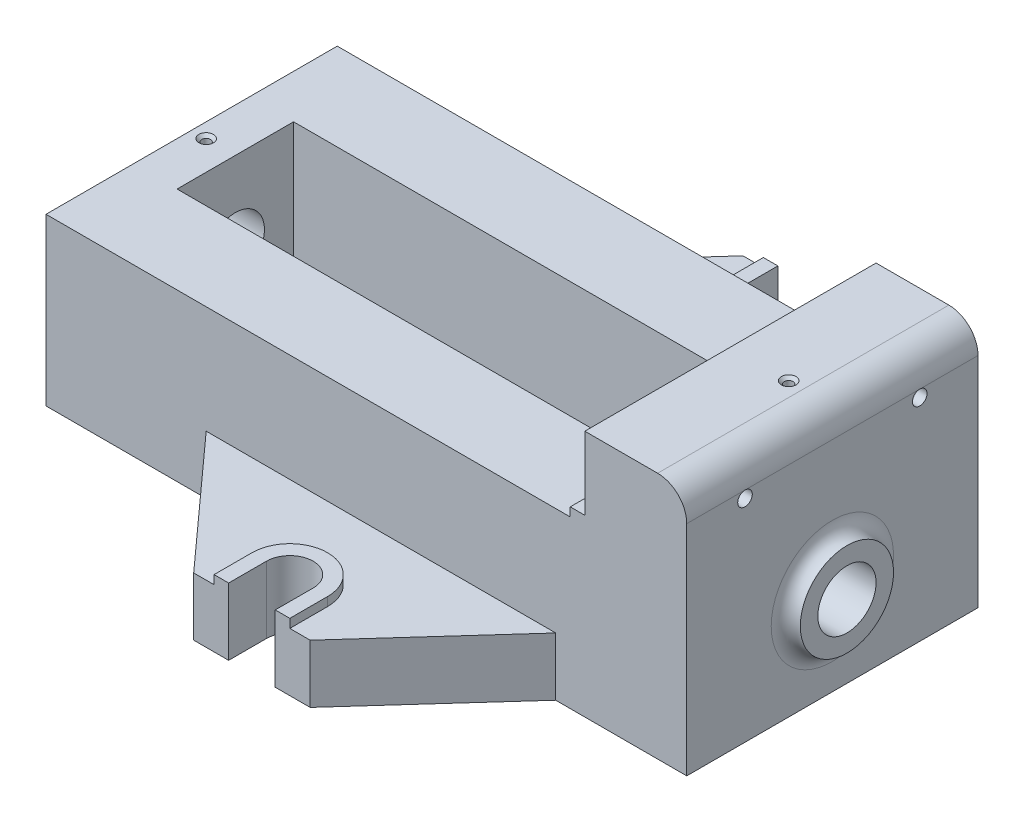
SolidWorks part; units mm, degrees
material "Gray Cast Iron"
ref_plane "Front Plane" through (0, 0, 0) normal (0, 0, 1) x (1, 0, 0)
ref_plane "Top Plane" through (0, 0, 0) normal (0, 1, 0) x (1, 0, 0)
ref_plane "Right Plane" through (0, 0, 0) normal (1, 0, 0) x (0, 0, -1)
sketch "Sketch1" plane through (0, 0, 0) normal (0, 0, 1) x (1, 0, 0)
  line L0 (0, 0) -> (220, 0)
  line L1 (220, 0) -> (220, 75)
  line L2 (210, 85) -> (185, 85)
  line L3 (185, 85) -> (185, 60)
  line L4 (185, 60) -> (180, 60)
  line L5 (180, 60) -> (180, 57)
  line L6 (180, 57) -> (0, 57)
  line L7 (0, 57) -> (0, 0)
  arc A0 (220, 75) -> (210, 85) centre (210, 75) ccw
  point P12 (220, 85)
  dimension "D7" = 10
  dimension "D1" = 220
  dimension "D2" = 85
  dimension "D3" = 57
  dimension "D4" = 25
  dimension "D5" = 5
  dimension "D6" = 35
extrude "Boss-Extrude1" add sketch "Sketch1" along normal mid plane 100
sketch "Sketch2" plane through (0, 0, 0) normal (-1, 0, 0) x (0, 0, 1)
  line L0 (0, 0) -> (0, 57) construction
  line L1 (50, 57) -> (-50, 57) construction
  line L2 (-30, 0) -> (-30, 10)
  line L3 (50, 0) -> (-50, 0) construction
  line L4 (-30, 10) -> (-26, 10)
  line L5 (-26, 10) -> (-26, 13)
  line L6 (-26, 13) -> (-20, 13)
  line L7 (-20, 13) -> (-20, 57)
  line L8 (-20, 57) -> (20, 57)
  line L9 (-30, 0) -> (30, 0)
  line L10 (30, 0) -> (30, 10)
  line L11 (30, 10) -> (26, 10)
  line L12 (26, 13) -> (20, 13)
  line L13 (20, 13) -> (20, 57)
  line L14 (26, 10) -> (26, 13)
  dimension "D1" = 30
  dimension "D2" = 26
  dimension "D3" = 20
  dimension "D4" = 10
  dimension "D5" = 13
extrude "Cut-Extrude1" cut sketch "Sketch2" against normal up to surface (180 mm away) from offset 15 up to face at (180, 58.5, 0) offset against normal yes
sketch "Sketch3" plane through (0, 0, 0) normal (-1, 0, 0) x (0, 0, 1)
  circle A0 centre (0, 30) radius 15
  dimension "D1" = 30
  dimension "D2" = 30
extrude "Boss-Extrude2" add sketch "Sketch3" along normal blind 5
sketch "Sketch4" plane through (220, 0, 0) normal (1, 0, 0) x (0, 0, -1)
  circle A0 centre (0, 30) radius 16
  dimension "D1" = 32
  dimension "D2" = 30
extrude "Boss-Extrude3" add sketch "Sketch4" along normal blind 5
sketch "Sketch5" plane through (225, 0, 0) normal (1, 0, 0) x (0, 0, -1)
  circle A0 centre (0, 30) radius 10
  dimension "D1" = 20
extrude "Cut-Extrude2" cut sketch "Sketch5" against normal through all
fillet "Fillet1" radius 5 2 edges at (220, 30, 16) (0, 15, 0)
sketch "Sketch6" plane through (185, 0, 0) normal (-1, 0, 0) x (0, 0, 1)
  line L0 (50, 85) -> (50, 60) construction
  line L1 (50, 60) -> (-50, 60) construction
  point P0 (-30, 72.5)
  point P1 (30, 72.5)
  dimension "D1" = 60
  dimension "D2" = 20
  dimension "D3" = 12.5
hole_wizard "Hole1" positions "3DSketch1" profile "Sketch7" legacy end condition through all
sketch3d "3DSketch1"
  point P0 (185, 72.5, -30)
  point P3 (185, 72.5, 30)
sketch "Sketch7" plane through (185, 72.5, -30) normal (0, 1, 0) x (0, 0, 1)
  line L0 (0, 0) -> (0, 41.5022)
  line L1 (0, 41.5022) -> (2.5, 40)
  line L2 (2.5, 40) -> (2.5, 10)
  line L3 (2.5, 10) -> (3, 10)
  line L4 (3, 0) -> (0, 0)
  line L5 (0, -11.3109) -> (0, 121.1557) construction
  line L6 (0, 41.5022) -> (-2.5, 40) construction
  line L7 (3, 10) -> (3, 0)
  dimension "Depth" = 40
  dimension "Drill Angle" = 118
  dimension "Diameter" = 5
  dimension "C-Bore Diameter" = 6
  dimension "C-Bore Depth" = 10
sketch "Sketch9" plane through (0, 85, 0) normal (0, 1, 0) x (1, 0, 0)
  line L0 (225, -16) -> (225, 16) construction
  point P0 (205, 0)
  dimension "D1" = 20
hole_wizard "Hole2" positions "3DSketch2" profile "Sketch10" legacy end condition through all
sketch3d "3DSketch2"
  point P0 (205, 85, 0)
sketch "Sketch10" plane through (205, 85, 0) normal (1, 0, 0) x (0, 0, 1)
  line L0 (0, 0) -> (0, 85)
  line L1 (0, 85) -> (1.5, 85)
  line L2 (1.5, 85) -> (1.5, 1)
  line L3 (1.5, 1) -> (2.5, 0)
  line L4 (2.5, 0) -> (0, 0)
  line L5 (0, -6.4453) -> (0, 115.525) construction
  line L6 (-1.5, 1) -> (-2.5, 0) construction
  dimension "Diameter" = 3
  dimension "Depth" = 85
  dimension "C-Sink Angle" = 90
  dimension "C-Sink Diameter" = 5
sketch "Sketch14" plane through (0, 57, 0) normal (0, 1, 0) x (1, 0, 0)
  line L0 (0, -50) -> (0, 50) construction
  point P0 (5, 0)
  dimension "D1" = 5
  dimension "D2" = 50
hole_wizard "Hole4" positions "3DSketch3" profile "Sketch15" legacy
sketch3d "3DSketch3"
  point P0 (5, 57, 0)
sketch "Sketch15" plane through (5, 57, 0) normal (1, 0, 0) x (0, 0, 1)
  line L0 (0, 0) -> (0, 57)
  line L1 (0, 57) -> (1.5, 57)
  line L2 (1.5, 57) -> (1.5, 1)
  line L3 (1.5, 1) -> (2.5, 0)
  line L4 (2.5, 0) -> (0, 0)
  line L5 (0, -6.4453) -> (0, 115.525) construction
  line L6 (-1.5, 1) -> (-2.5, 0) construction
  dimension "Diameter" = 3
  dimension "Depth" = 57
  dimension "C-Sink Angle" = 90
  dimension "C-Sink Diameter" = 5
sketch "Sketch16" plane through (0, 57, 0) normal (0, 1, 0) x (1, 0, 0)
  line L0 (175, -50) -> (135, -94.2916)
  line L1 (180, -50) -> (0, -50) construction
  line L2 (135, -94.2916) -> (123, -94.2916)
  line L3 (95, -94.2916) -> (55, -50)
  line L4 (55, -50) -> (175, -50)
  line L5 (107, -81.2916) -> (107, -94.2916)
  line L6 (123, -81.2916) -> (123, -94.2916)
  line L7 (107, -94.2916) -> (95, -94.2916)
  arc A0 (123, -81.2916) -> (107, -81.2916) centre (115, -81.2916) ccw
  dimension "D5" = 16
  dimension "D1" = 55
  dimension "D2" = 40
  dimension "D3" = 120
  dimension "D4" = 40
  dimension "D6" = 13
sketch "Sketch17" plane through (0, 57, 0) normal (0, 1, 0) x (1, 0, 0)
  line L0 (128, 94.2916) -> (128, 81.2916)
  line L1 (102, 81.2916) -> (102, 94.2916)
  line L2 (102, 94.2916) -> (107, 94.2916)
  line L3 (123, 94.2916) -> (128, 94.2916)
  arc A0 (102, 81.2916) -> (128, 81.2916) centre (115, 81.2916) ccw
sketch "Sketch18" plane through (0, 0, 0) normal (0, -1, 0) x (1, 0, 0)
  line L0 (55, 50) -> (95, 94.2916)
  line L1 (95, 94.2916) -> (107, 94.2916)
  line L2 (107, 94.2916) -> (107, 81.2916)
  line L3 (123, 81.2916) -> (123, 94.2916)
  line L4 (123, 94.2916) -> (135, 94.2916)
  line L5 (135, 94.2916) -> (175, 50)
  line L6 (102, -94.2916) -> (107, -94.2916) construction
  line L7 (128, -94.2916) -> (128, -81.2916) construction
  line L8 (102, -81.2916) -> (102, -94.2916) construction
  line L9 (102, -94.2916) -> (107, -94.2916)
  line L10 (128, -94.2916) -> (128, -81.2916)
  line L11 (102, -81.2916) -> (102, -94.2916)
  line L12 (123, -94.2916) -> (128, -94.2916) construction
  line L13 (123, -94.2916) -> (128, -94.2916)
  line L14 (55, 50) -> (175, 50)
  arc A0 (107, 81.2916) -> (123, 81.2916) centre (115, 81.2916) ccw
  arc A1 (128, -81.2916) -> (102, -81.2916) centre (115, -81.2916) ccw construction
  arc A2 (128, -81.2916) -> (102, -81.2916) centre (115, -81.2916) ccw
  point P11 (123, -94.2916)
extrude "Boss-Extrude7" add sketch "Sketch18" against normal blind 20 contours L5 L14 L0 L1 L2 A0 L3 L4
mirror "Mirror4" about plane through (0, 0, 0) normal (0, 0, 1) of "Boss-Extrude7"
sketch "Sketch21" plane through (0, 20, 0) normal (0, 1, 0) x (1, 0, 0)
  line L0 (128, 94.2916) -> (128, 81.2916)
  line L1 (102, 81.2916) -> (102, 94.2916)
  line L2 (102, 94.2916) -> (107, 94.2916)
  line L3 (123, 94.2916) -> (128, 94.2916)
  line L7 (135, 94.2916) -> (123, 94.2916)
  line L8 (123, 94.2916) -> (123, 81.2916)
  line L9 (107, 81.2916) -> (107, 94.2916)
  line L10 (107, 94.2916) -> (95, 94.2916)
  line L11 (95, 94.2916) -> (55, 50)
  line L12 (55, 50) -> (175, 50)
  line L13 (175, 50) -> (135, 94.2916)
  line L15 (123, 94.2916) -> (123, 81.2916)
  line L16 (107, 81.2916) -> (107, 94.2916)
  arc A0 (102, 81.2916) -> (128, 81.2916) centre (115, 81.2916) ccw
  arc A1 (107, 81.2916) -> (123, 81.2916) centre (115, 81.2916) ccw
  arc A2 (107, 81.2916) -> (123, 81.2916) centre (115, 81.2916) ccw
  dimension "D1" = 0
  dimension "D2" = 5
extrude "Boss-Extrude9" add sketch "Sketch21" along normal blind 3 contours A2 L15 L3 L0 A0 L1 L2 L16
mirror "Mirror5" about plane through (0, 0, 0) normal (0, 0, 1) of "Boss-Extrude9"
